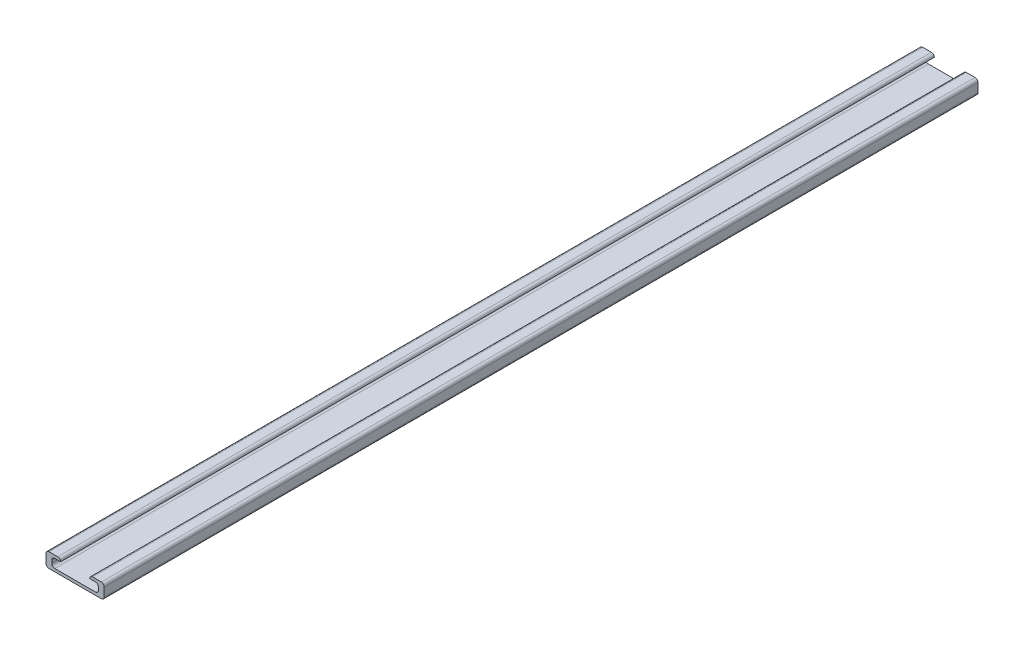
SolidWorks part; units mm, degrees
ref_plane "Front Plane" through (0, 0, 0) normal (0, 0, 1) x (1, 0, 0)
ref_plane "Top Plane" through (0, 0, 0) normal (0, 1, 0) x (1, 0, 0)
ref_plane "Right Plane" through (0, 0, 0) normal (1, 0, 0) x (0, 0, -1)
sketch "Sketch1" plane through (0, 0, 0) normal (0, 0, 1) x (1, 0, 0)
  line L0 (0, 0) -> (-20, 0)
  line L1 (0, 0) -> (0, 5)
  line L2 (0, 5) -> (-5, 5)
  line L3 (-20, 5) -> (-20, 0)
  line L4 (0, 5) -> (-0.036, 4.9939)
  line L5 (-20, 5) -> (-15, 5)
  line L6 (0, 5) -> (-5, 5)
  line L7 (-5, 5) -> (-5, 4)
  line L8 (-5, 4) -> (-2, 4)
  line L9 (-2, 4) -> (-2, 1)
  line L10 (-2, 1) -> (-18, 1)
  line L11 (-18, 1) -> (-18, 4)
  line L12 (-18, 4) -> (-15, 4)
  line L13 (-15, 4) -> (-15, 5)
  line L14 (-15, 5) -> (-20, 5)
  dimension "D1" = 20
  dimension "D2" = 5
  dimension "D3" = 5
  dimension "D4" = 5
  dimension "D5" = 1
  dimension "D6" = 1
  dimension "D7" = 1
  dimension "D8" = 2
  dimension "D9" = 2
extrude "Boss-Extrude1" add sketch "Sketch1" along normal blind 300 contours L12 L13 L5 L3 L0 L1 L2 L7 L8 L9 L10 L11 region at (-10, 0.2062, 0)
fillet "Fillet2" radius 1 10 edges at (-18, 4, 150) (-2, 4, 150) (-2, 1, 150) (-18, 1, 150) (-20, 0, 150) (-20, 5, 150) (-15, 5, 150) (0, 0, 150) (0, 5, 150) (-5, 5, 150)
